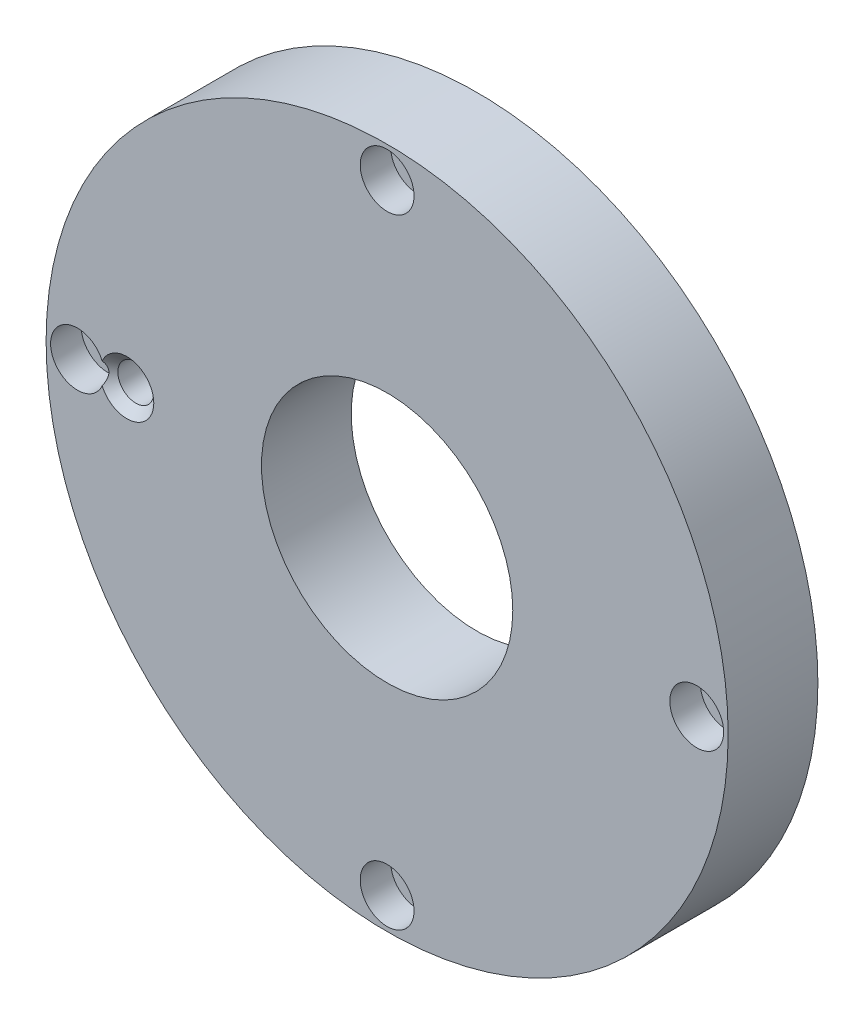
SolidWorks part; units mm, degrees
material "AISI 1020"
ref_plane "前视基准面" through (0, 0, 0) normal (0, 0, 1) x (1, 0, 0)
ref_plane "上视基准面" through (0, 0, 0) normal (0, 1, 0) x (1, 0, 0)
ref_plane "右视基准面" through (0, 0, 0) normal (1, 0, 0) x (0, 0, -1)
sketch "草图1" plane through (0, 0, 0) normal (0, 0, 1) x (1, 0, 0)
  circle A0 centre (0, 0) radius 38
  circle A1 centre (0, 0) radius 14
  dimension "D1" = 76
  dimension "D2" = 28
extrude "凸台-拉伸1" add sketch "草图1" along normal blind 10
hole_wizard "打孔尺寸(%根据)内六角圆柱头螺钉的类型1" positions "草图4" profile "草图5" counterbore size "M3" standard "GB" end condition up to next
sketch "草图4" plane through (0, 0, 10) normal (0, 0, 1) x (1, 0, 0)
  circle A0 centre (0, 0) radius 34.5 construction
  point P0 (0, 34.5)
  point P16 (34.5, 0)
  point P17 (0, -34.5)
  point P18 (-34.5, 0)
  dimension "D1" = 69
  dimension "D2" = 4
sketch "草图5" plane through (0, 34.5, 10) normal (1, 0, 0) x (0, -1, 0)
  line L0 (0, 0) -> (0, 10)
  line L1 (0, 10) -> (1.6, 10)
  line L3 (1.6, 10) -> (1.6, 3.4)
  line L4 (1.6, 3.4) -> (3, 3.4)
  line L5 (3, 3.4) -> (3, 0)
  line L7 (3, 0) -> (0, 0)
  line L11 (0, -6.35) -> (0, 107.95) construction
  dimension "通孔孔直径" = 3.2
  dimension "通孔孔深度" = 10
  dimension "柱形沉头孔直径" = 6
  dimension "柱形沉头孔深度" = 3.4
hole_wizard "Ø4.0 (4) 直径孔1" positions "草图8" profile "草图7" hole size "Ø4.0" standard "GB" end condition up to next
sketch "草图8" plane through (0, 0, 0) normal (0, 0, -1) x (-1, 0, 0)
  line L0 (0, 0) -> (30.5332, 0) construction
  line L2 (0, 0) -> (0, -10.3474) construction
  circle A1 centre (0, 0) radius 14 construction
  point P0 (29, 0)
  dimension "D1" = 15
  dimension "D2" = 90
sketch "草图7" plane through (-29, 0, 0) normal (1, 0, 0) x (0, 1, 0)
  line L0 (0, 0) -> (0, 10)
  line L1 (0, 10) -> (2, 10)
  line L2 (2, 10) -> (2, 0)
  line L5 (2, 0) -> (0, 0)
  line L11 (0, -6.35) -> (0, 107.95) construction
  dimension "通孔孔直径" = 4
  dimension "通孔孔深度" = 10
chamfer "倒角1" distance 1 angle 45 2 edges at (-31, 0, 0) (-27, 0, 10)
